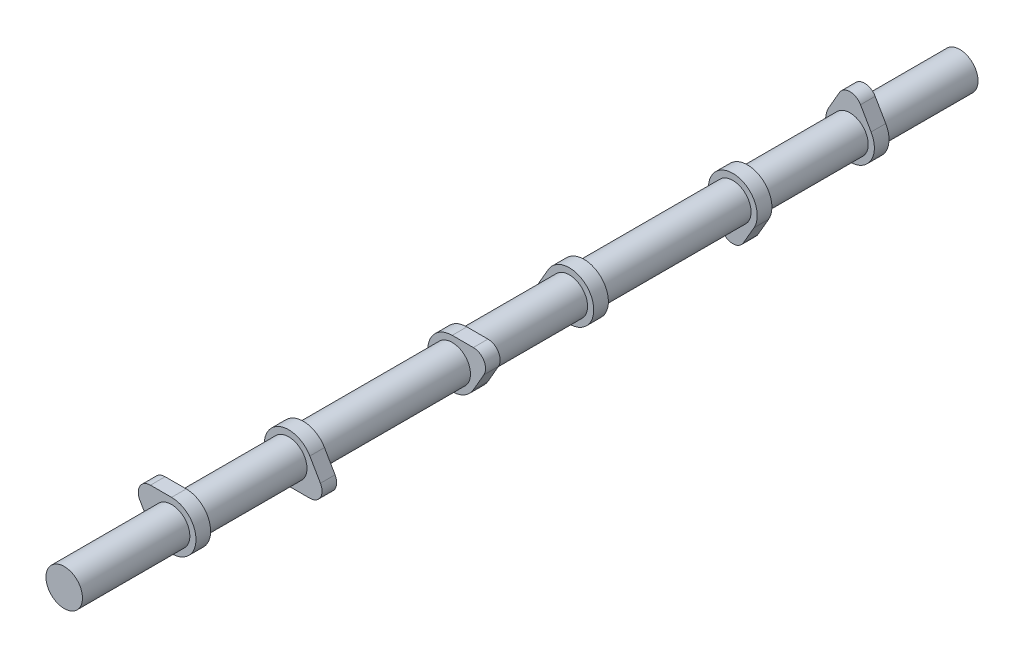
SolidWorks part; units mm, degrees
ref_plane "Plan de face" through (0, 0, 0) normal (0, 0, 1) x (1, 0, 0)
ref_plane "Plan de dessus" through (0, 0, 0) normal (0, 1, 0) x (1, 0, 0)
ref_plane "Plan de droite" through (0, 0, 0) normal (1, 0, 0) x (0, 0, -1)
sketch "Esquisse1" plane through (0, 0, 0) normal (0, 0, 1) x (1, 0, 0)
  line L0 (-5.4993, 15.875) -> (-10.9985, 6.35)
  line L1 (5.4993, 15.875) -> (10.9985, 6.35)
  arc A0 (-10.9985, 6.35) -> (10.9985, 6.35) centre (0, 0) ccw
  arc A1 (5.4993, 15.875) -> (-5.4993, 15.875) centre (0, 12.7) ccw
  dimension "D1" = 25.4
  dimension "D2" = 12.7
  dimension "D3" = 12.7
extrude "Boss.-Extru.1" add sketch "Esquisse1" along normal mid plane 7.62
ref_axis "Axe1" through (0, 0, 86.6438) along (0, 0, -1)
move or copy body "Corps-Déplacer/Copier1" bodies to move or copy 101 copy yes number of copies 1 translate (0, 0, 60.96) parameters "D1"=0, "D2"=0, "D3"=0
move or copy body "Corps-Déplacer/Copier2" bodies to move or copy 102 copy no rotation origin (0, 0, 0) rotation axis (0, 0, 1) rotation angle 180
sketch "Esquisse4" plane through (0, 0, 0) normal (0, 0, 1) x (1, 0, 0)
  circle A0 centre (0, 0) radius 9.5
  dimension "D1" = 19
extrude "Boss.-Extru.2" add sketch "Esquisse4" along normal blind 146.05 from offset 25.4 offset against normal yes
pattern_linear "Répétition linéaire2" count 3 spacing 146.05 along (0, 0, 1) of bodies 104
move or copy body "Corps-Déplacer/Copier3" bodies to move or copy 106 copy no rotation origin (0, 0, 0) rotation axis (0, 0, 1) rotation angle 120
move or copy body "Corps-Déplacer/Copier4" bodies to move or copy 107 copy no rotation origin (0, 0, 0) rotation axis (0, 0, -1) rotation angle 120
sketch "Esquisse5" plane through (0, 0, -25.4) normal (0, 0, -1) x (-1, 0, 0)
  circle A1 centre (0, 0) radius 9.5
  circle A2 centre (0, 0) radius 9.5
  dimension "D1" = 0
extrude "Boss.-Extru.3" add sketch "Esquisse5" along normal blind 27.94
combine bodies "Combiner1" operation type add bodies to combine 109 108 110
